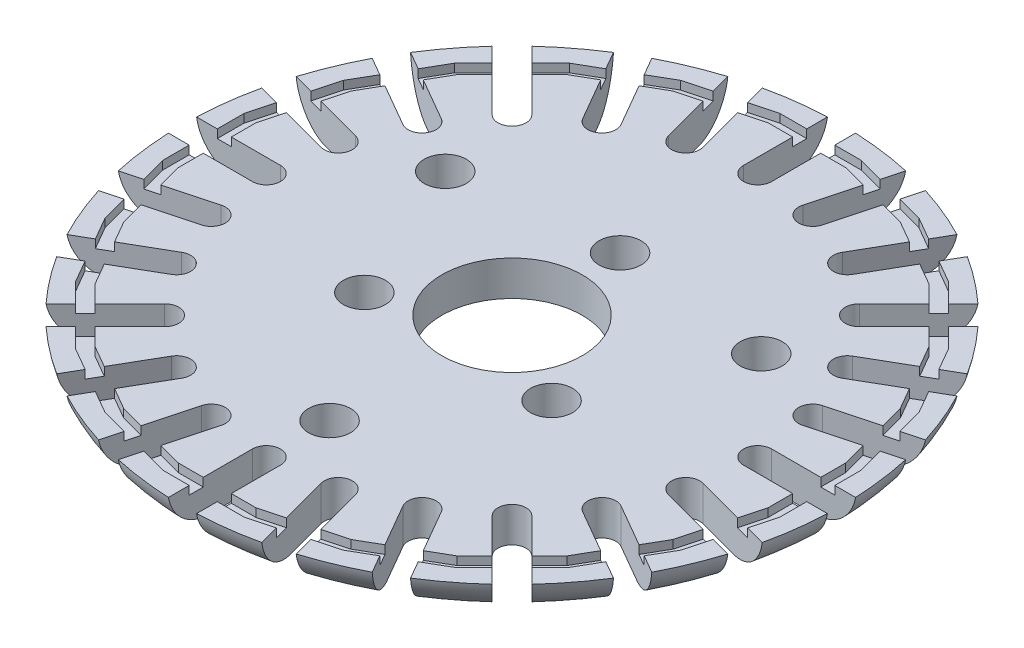
SolidWorks part; units mm, degrees
ref_plane "Plano frontal" through (0, 0, 0) normal (0, 0, 1) x (1, 0, 0)
ref_plane "Plano superior" through (0, 0, 0) normal (0, 1, 0) x (1, 0, 0)
ref_plane "Plano direito" through (0, 0, 0) normal (1, 0, 0) x (0, 0, -1)
sketch "Esboço1" plane through (0, 0, 0) normal (0, 1, 0) x (1, 0, 0)
  circle A0 centre (0, 0) radius 23.5
  dimension "D1" = 47
extrude "Ressalto-extrusão1" add sketch "Esboço1" along normal blind 2.5
fillet "Filete1" radius 3 1 edges at (0, 0, 23.5)
sketch "Esboço2" plane through (0, 2.5, 0) normal (0, 1, 0) x (1, 0, 0)
  line L0 (0, 0) -> (0, 23.9078) construction
  line L2 (1, 17.5) -> (1, 23.5)
  line L3 (1, 23.5) -> (-1, 23.5)
  line L4 (0, 23.5) -> (7.8408, 23.5) construction
  line L5 (-1, 17.5) -> (-1, 23.5)
  arc A0 (-1, 17.5) -> (1, 17.5) centre (0, 17.5) ccw
  circle A3 centre (0, 0) radius 23.5 construction
  point P12 (0, 16.5)
  dimension "D2" = 6
  dimension "D1" = 1
extrude "Corte-extrusão1" cut sketch "Esboço2" against normal through all
pattern_circular "PadrãoCircular1" count 24 over 360 about axis through (0, 2.5, 0) along (0, 1, 0) of "Corte-extrusão1"
sketch "Esboço4" plane through (0, 2.5, 0) normal (0, 1, 0) x (1, 0, 0)
  line L0 (0, 0) -> (-3.0674, 23.299) construction
  line L1 (0, 0) -> (3.0674, 23.299) construction
  line L2 (-2.8964, 22) -> (2.8964, 22)
  line L3 (2.8964, 22) -> (2.7647, 21)
  line L4 (2.7647, 21) -> (-2.7647, 21)
  line L5 (-2.7647, 21) -> (-2.8964, 22)
  arc A2 (5.1108, 22.9375) -> (1, 23.4787) centre (0, 0) ccw construction
  arc A3 (-1, 23.4787) -> (-5.1108, 22.9375) centre (0, 0) ccw construction
  dimension "D1" = 1
  dimension "D2" = 21
extrude "Corte-extrusão2" cut sketch "Esboço4" against normal blind 0.6
pattern_circular "PadrãoCircular2" count 24 over 360 about axis through (0, 2.5, 0) along (0, 1, 0) of "Corte-extrusão2"
sketch "Esboço5" plane through (0, 2.5, 0) normal (0, 1, 0) x (1, 0, 0)
  circle A0 centre (0, 0) radius 5
  dimension "D1" = 10
extrude "Corte-extrusão3" cut sketch "Esboço5" against normal through all
sketch "Esboço6" plane through (0, 2.5, 0) normal (0, 1, 0) x (1, 0, 0)
  circle A1 centre (0, 7.7) radius 1.5
  circle A2 centre (-6.6684, -3.85) radius 1.5
  circle A3 centre (6.6684, -3.85) radius 1.5
  circle A4 centre (-11.2583, 6.5) radius 1.5
  circle A5 centre (11.2583, 6.5) radius 1.5
  circle A6 centre (0, -13) radius 1.5
  dimension "D1" = 3
  dimension "D2" = 7.7
  dimension "D5" = 3
  dimension "D3" = 7.7
  dimension "D4" = 7.7
extrude "Corte-extrusão5" cut sketch "Esboço6" against normal blind 2.5
